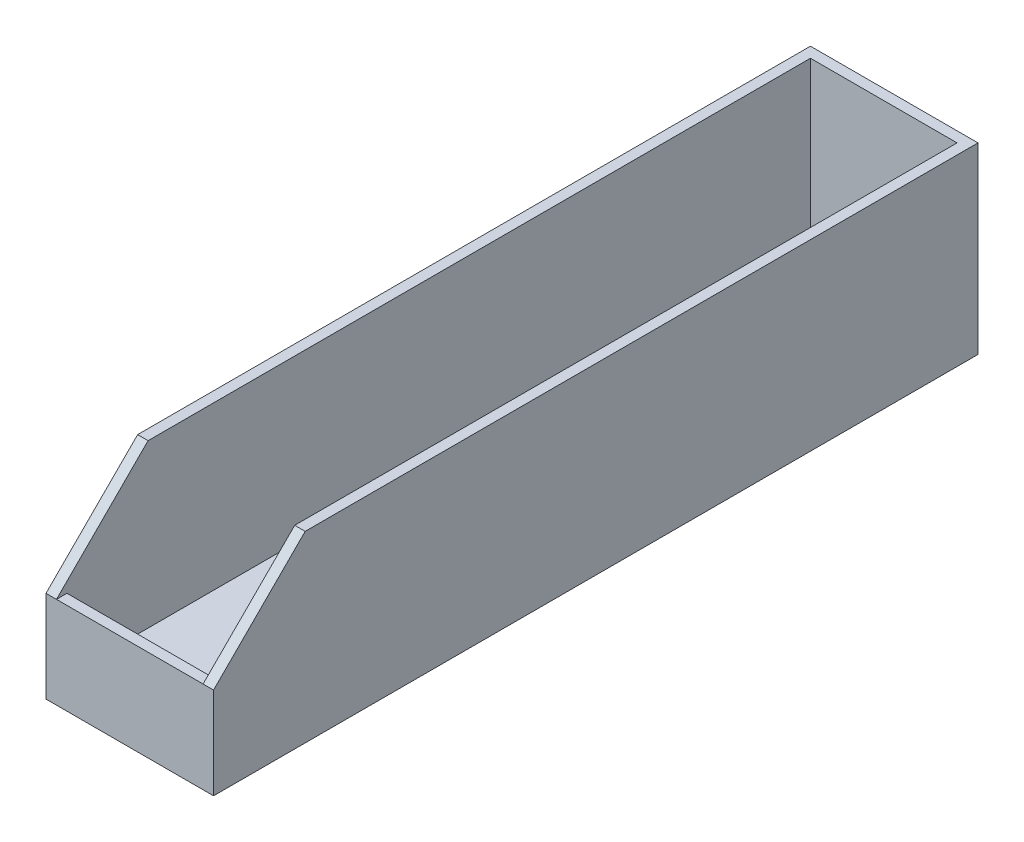
SolidWorks part; units mm, degrees
ref_plane "Front Plane" through (0, 0, 0) normal (0, 0, 1) x (1, 0, 0)
ref_plane "Top Plane" through (0, 0, 0) normal (0, 1, 0) x (1, 0, 0)
ref_plane "Right Plane" through (0, 0, 0) normal (1, 0, 0) x (0, 0, -1)
sketch "Sketch1" plane through (0, 0, 0) normal (0, 1, 0) x (1, 0, 0)
  line L0 (-14, -71) -> (-14, -73)
  line L1 (-16, 73) -> (16, 73)
  line L2 (-16, 73) -> (-16, -73)
  line L3 (-16, -73) -> (16, -73)
  line L4 (16, 73) -> (16, -73)
  line L5 (-16, 73) -> (16, -73) construction
  line L6 (-16, -73) -> (16, 73) construction
  line L7 (-14, 71) -> (14, 71)
  line L8 (-14, 71) -> (-14, -71)
  line L9 (-14, -71) -> (14, -71)
  line L10 (14, 71) -> (14, -71)
  line L11 (-14, 71) -> (14, -71) construction
  line L12 (-14, -71) -> (14, 71) construction
  line L13 (14, -71) -> (14, -73)
  point P0 (0, 0)
  point P6 (0, 0)
  dimension "D1" = 146
  dimension "D2" = 28
  dimension "D3" = 32
  dimension "D4" = 142
extrude "Boss-Extrude1" add sketch "Sketch1" along normal blind 4 contours L10 L7 L8 L9 region at (0, 0, 0)
extrude "Boss-Extrude2" add sketch "Sketch1<4>" along normal blind 35 contours L10 L13 L3 L4 L1 L2 L0 L8 L7 region at (-15.4947, 0, 72)
sketch "Sketch1<4>" plane through (0, 0, 0) normal (0, 1, 0) x (1, 0, 0) same geometry as "Sketch1"
extrude "Boss-Extrude3" add sketch "Sketch1<5>" along normal blind 17.5 contours L13 L9 L0 L3 region at (0, 0, 72)
sketch "Sketch1<5>" plane through (0, 0, 0) normal (0, 1, 0) x (1, 0, 0) same geometry as "Sketch1"
sketch "Sketch2" plane through (0, 4, 0) normal (0, 1, 0) x (1, 0, 0)
  line L0 (0, 30) -> (0, -30) construction
  circle A0 centre (0, 30) radius 3.15
  circle A1 centre (0, 30) radius 1.75
  circle A2 centre (0, -30) radius 3.15
  circle A3 centre (0, -30) radius 1.75
  point P6 (0, 0)
  dimension "D1" = 3.5
  dimension "D2" = 6.3
  dimension "D3" = 30
extrude "Cut-Extrude1" cut sketch "Sketch2" against normal up to next contours A1 | A3 region at (0, 4, -30) region at (0, 4, 30)
extrude "Cut-Extrude2" cut sketch "Sketch2<3>" against normal blind 2 contours A2 A3 | A1 A0 region at (-3.0609, 4, -30) region at (-3.0609, 4, 30)
sketch "Sketch2<3>" plane through (0, 4, 0) normal (0, 1, 0) x (1, 0, 0) same geometry as "Sketch2"
sketch "Sketch3" plane through (16, 0, 0) normal (1, 0, 0) x (0, 0, -1)
  line L0 (-73, 17.5) -> (-55.5, 35)
  line L1 (-73, 35) -> (-73, 0) construction
  line L2 (73, 35) -> (-73, 35) construction
  line L3 (-55.5, 35) -> (-73, 35)
  line L4 (-73, 35) -> (-73, 17.5)
extrude "Cut-Extrude3" cut sketch "Sketch3" against normal through all
